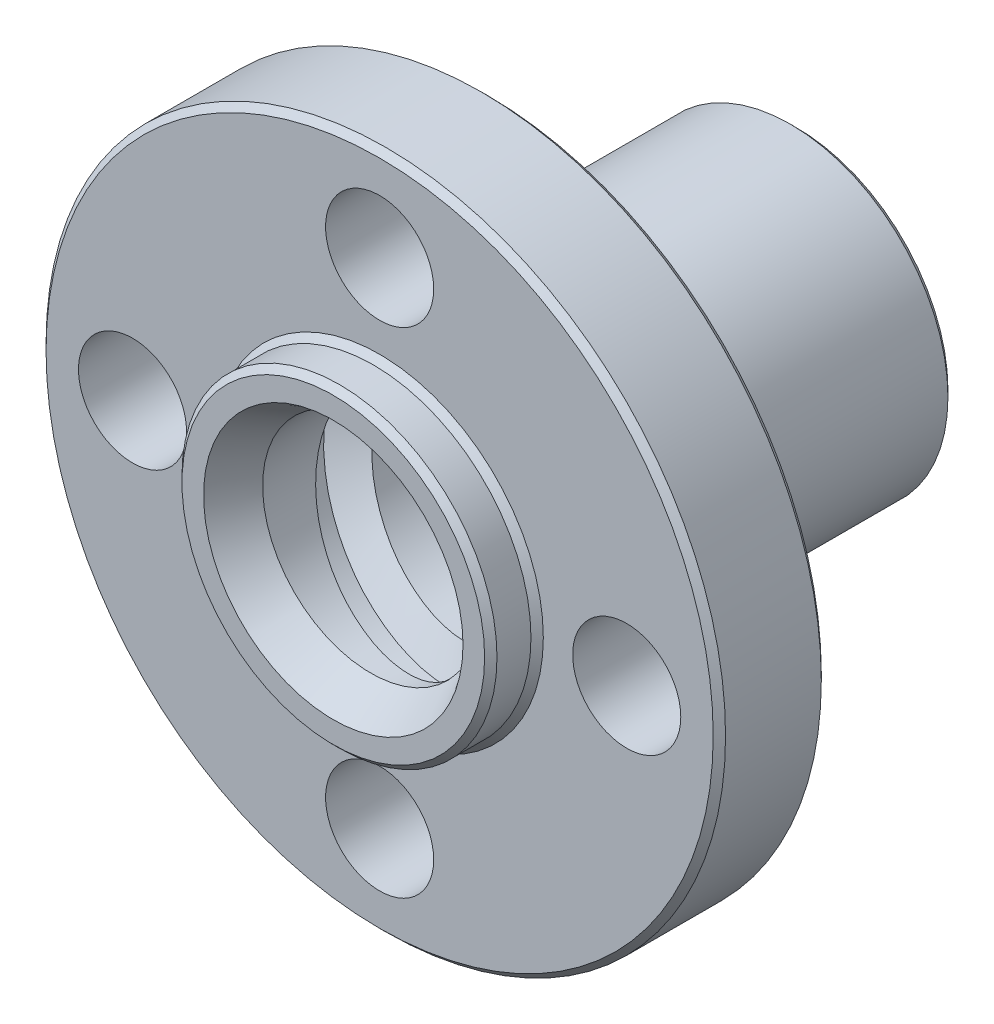
SolidWorks part; units mm, degrees
ref_plane "Plan de face" through (0, 0, 0) normal (0, 0, 1) x (1, 0, 0)
ref_plane "Plan de dessus" through (0, 0, 0) normal (0, 1, 0) x (1, 0, 0)
ref_plane "Plan de droite" through (0, 0, 0) normal (1, 0, 0) x (0, 0, -1)
sketch "Esquisse1" plane through (0, 0, 0) normal (0, 0, 1) x (1, 0, 0)
  circle A0 centre (0, 0) radius 8 construction
  circle A1 centre (0, 0) radius 5.1
  circle A2 centre (0, 0) radius 11
  circle A3 centre (0, 8) radius 1.75
  circle A4 centre (0, 0) radius 8 construction
  circle A5 centre (8, 0) radius 1.75
  circle A6 centre (0, 0) radius 8 construction
  circle A7 centre (0, -8) radius 1.75
  circle A8 centre (0, 0) radius 8 construction
  circle A9 centre (-8, 0) radius 1.75
  point P19 (0, 0)
  dimension "D1" = 22
  dimension "D2" = 16
  dimension "D3" = 10.2
  dimension "D4" = 3.5
  dimension "D5" = 4
extrude "Boss.-Extru.1" add sketch "Esquisse1" along normal blind 3.5
sketch "Esquisse2" plane through (0, 0, 3.5) normal (0, 0, 1) x (1, 0, 0)
  circle A0 centre (0, 0) radius 5.1 construction
  circle A1 centre (0, 0) radius 5.1
  circle A2 centre (0, 0) radius 3.5
  dimension "D1" = 7
extrude "Boss.-Extru.2" add sketch "Esquisse2" along normal blind 1.5 and the other way blind 13.5
chamfer "Chanfrein2" distance 0.7 angle 60 2 edges at (3.5, 0, 5) (3.5, 0, -10)
sketch "Esquisse5" plane through (0, 0, 3.5) normal (0, 0, 1) x (1, 0, 0)
  circle A0 centre (0, 0) radius 4.2 construction
  circle A1 centre (0, 0) radius 4.2
curve "Hélice/Spirale1" pitch 4.5 height 25 turns 5.5556
sketch "Esquisse6" plane through (0, 0, 0) normal (1, 0, 0) x (0, 0, -1)
  line L0 (9.367, 4.5) -> (8.7037, 4.5)
  line L1 (8.7037, 4.5) -> (7.4092, 2.2579)
  line L2 (7.4092, 2.2579) -> (10.6615, 2.2579)
  line L3 (9.0353, 4.5) -> (9.0353, 2.2579) construction
  line L4 (9.367, 4.5) -> (10.6615, 2.2579)
  line L5 (10, 5.1) -> (0, 5.1) construction
  dimension "D1" = 60
  dimension "D2" = 0.6
sweep "Enlèvement de matière-Balayage1" cut profiles "Esquisse6" path "Hélice/Spirale1"
chamfer "Chanfrein3" distance 0.2 angle 45 6 edges at (5.1, 0, -10) (11, 0, 0) (5.1, 0, 3.5) (5.1, 0, 5) (11, 0, 3.5) (5.1, 0, 0)
